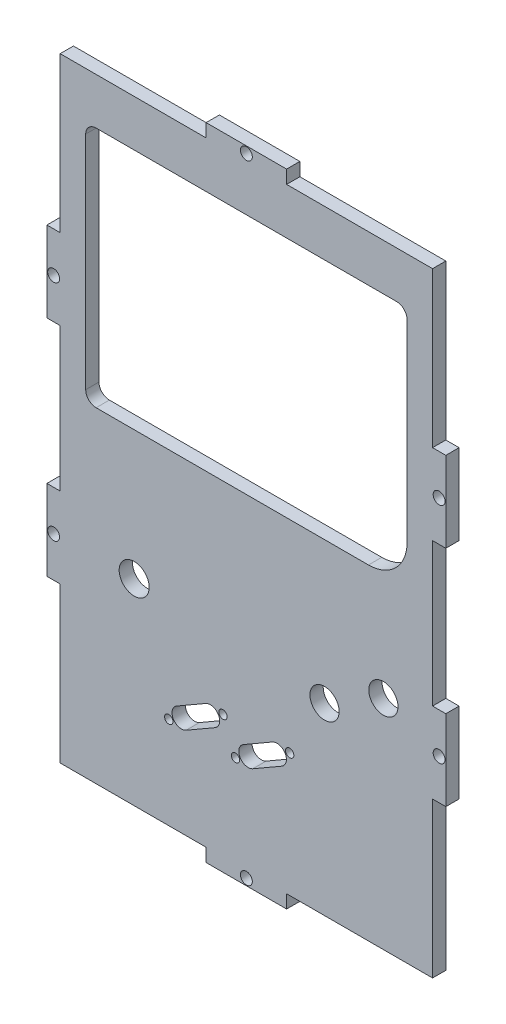
SolidWorks part; units mm, degrees
ref_plane "Front Plane" through (0, 0, 0) normal (0, 0, 1) x (1, 0, 0)
ref_plane "Top Plane" through (0, 0, 0) normal (0, 1, 0) x (1, 0, 0)
ref_plane "Right Plane" through (0, 0, 0) normal (1, 0, 0) x (0, 0, -1)
sketch "Sketch1" plane through (0, 0, 0) normal (0, 0, 1) x (1, 0, 0)
  line L0 (0, 73.6471) -> (0, 62.5071) construction
  line L1 (0, 62.5071) -> (0, 56.2171) construction
  line L2 (0, 56.2171) -> (0, 10.2844) construction
  line L3 (-12.1109, -47.7971) -> (3.8891, -47.7971) construction
  line L4 (-2.6061, -51.5471) -> (10.3843, -44.0471) construction
  line L5 (0.425, -49.7971) -> (7.3532, -45.7971) construction
  line L6 (0, 10.2844) -> (0, -73.6471) construction
  line L7 (-18.6061, -51.5471) -> (-5.6157, -44.0471) construction
  line L8 (-0.7, -47.8486) -> (6.2282, -43.8486)
  line L9 (1.55, -51.7457) -> (8.4782, -47.7457)
  line L15 (-16.3293, -29.1587) -> (-16.3293, -23.8757)
  line L16 (0, 0) -> (-44.645, 0) construction
  line L17 (0, 0) -> (44.645, 0) construction
  line L18 (-36.025, 60.0071) -> (-38.525, 60.0071) construction
  line L19 (29.275, 4.4344) -> (29.275, 13.6844) construction
  line L22 (-44.645, 73.6471) -> (44.645, 73.6471)
  line L23 (44.645, 73.6471) -> (44.645, -73.6471)
  line L24 (44.645, -73.6471) -> (-44.645, -73.6471)
  line L25 (-44.645, -73.6471) -> (-44.645, 73.6471)
  line L26 (-25.1657, 56.2171) -> (-25.1657, 10.2844)
  line L27 (-25.1657, 10.2844) -> (25.1657, 10.2844)
  line L28 (25.1657, 10.2844) -> (25.1657, 56.2171)
  line L29 (25.1657, 56.2171) -> (-25.1657, 56.2171)
  line L30 (29.275, 13.6844) -> (38.525, 13.6844) construction
  line L31 (-36.025, 62.5071) -> (-36.025, 60.0071) construction
  line L34 (36.025, 62.5071) -> (-36.025, 62.5071)
  line L35 (-38.525, 60.0071) -> (-38.525, 6.9344)
  line L36 (-36.025, 4.4344) -> (29.275, 4.4344)
  line L37 (38.525, 13.6844) -> (38.525, 60.0071)
  line L42 (-15.575, -49.7971) -> (-8.6468, -45.7971) construction
  line L43 (-16.7, -47.8486) -> (-9.7718, -43.8486)
  line L44 (-14.45, -51.7457) -> (-7.5218, -47.7457)
  line L45 (-16.7, -47.8486) -> (-14.45, -51.7457) construction
  line L46 (-9.7718, -43.8486) -> (-7.5218, -47.7457) construction
  line L150 (42.2525, -55.0539) -> (42.2511, -54.9499)
  circle A1 centre (-5.6157, -44.0471) radius 1
  circle A2 centre (-26.9008, -26.5172) radius 3.6
  circle A4 centre (-18.6061, -51.5471) radius 1
  arc A13 (-16.7, -47.8486) -> (-14.45, -51.7457) centre (-15.575, -49.7971) ccw
  arc A14 (-7.5218, -47.7457) -> (-9.7718, -43.8486) centre (-8.6468, -45.7971) ccw
  circle A15 centre (18.7439, -29.5449) radius 3.5
  circle A16 centre (32.8547, -21.4753) radius 3.5
  circle A18 centre (10.3843, -44.0471) radius 1
  circle A19 centre (-32.9517, 40.3431) radius 4.5
  circle A20 centre (-2.6061, -51.5471) radius 1
  arc A21 (-0.7, -47.8486) -> (1.55, -51.7457) centre (0.425, -49.7971) ccw
  arc A22 (8.4782, -47.7457) -> (6.2282, -43.8486) centre (7.3532, -45.7971) ccw
  arc A24 (38.525, 60.0071) -> (36.025, 62.5071) centre (36.025, 60.0071) ccw
  arc A25 (-36.025, 62.5071) -> (-38.525, 60.0071) centre (-36.025, 60.0071) ccw
  arc A26 (-38.525, 6.9344) -> (-36.025, 4.4344) centre (-36.025, 6.9344) ccw
  arc A27 (29.275, 4.4344) -> (38.525, 13.6844) centre (29.275, 13.6844) ccw
  point P31 (-12.1109, -47.7971)
  point P47 (3.8891, -47.7971)
  point P53 (3.8891, -47.7971)
  point P54 (-12.1109, -47.7971)
  dimension "D4" = 11.14
  dimension "D8" = 7
  dimension "D11" = 9
  dimension "D12" = 7.2
  dimension "D14" = 9.25
  dimension "D15" = 2.5
  dimension "D25" = 2
  dimension "D27" = 4.5
  dimension "D2" = 89.29
  dimension "D3" = 147.2943
  dimension "D5" = 25.9097
  dimension "D6" = 8.0696
  dimension "D7" = 14.1107
  dimension "D9" = 7.7861
  dimension "D10" = 22.1641
  dimension "D13" = 10.5715
  dimension "D16" = 6.29
  dimension "D17" = 6.12
  dimension "D18" = 5.85
  dimension "D19" = 32.5341
  dimension "D20" = 25.85
  dimension "D21" = 16
  dimension "D22" = 8
  dimension "D24" = 15
  dimension "D26" = 90
extrude "Body" add sketch "Sketch1<7>" along normal blind 3.18 contours L25 L24 L23 L22 A27 L36 A26 L35 A25 L34 A24 L37 A16 A15 A2 region at (0.0244, -16.6397, 0)
sketch "Sketch1<7>" plane through (0, 0, 0) normal (0, 0, 1) x (1, 0, 0) same geometry as "Sketch1"
extrude "Buttons" [suppressed] add sketch "Sketch1" along normal blind 3.18 contours A19 | A2 | A15 | A16
sketch "Sketch2" plane through (0, 73.6471, 0) normal (0, 1, 0) x (1, 0, 0)
  line L0 (-9.65, 0) -> (9.65, 0)
  line L1 (-44.645, 0) -> (44.645, 0) construction
  line L2 (9.65, 0) -> (9.65, -3.18)
  line L3 (-44.645, -3.18) -> (44.645, -3.18) construction
  line L4 (9.65, -3.18) -> (-9.65, -3.18)
  line L5 (-9.65, -3.18) -> (-9.65, 0)
  line L6 (0, 0) -> (0, -3.18) construction
  dimension "D1" = 19.3
extrude "Boss-Extrude1" add sketch "Sketch2" along normal blind 3.18
sketch "Sketch3" plane through (0, 0, 3.18) normal (0, 0, 1) x (1, 0, 0)
  line L0 (-9.65, 75.2371) -> (9.65, 75.2371) construction
  line L1 (-9.65, 76.8271) -> (-9.65, 73.6471) construction
  line L2 (9.65, 76.8271) -> (9.65, 73.6471) construction
  line L3 (0, 76.8271) -> (0, 73.4734) construction
  line L4 (-9.65, 76.8271) -> (9.65, 76.8271) construction
  circle A0 centre (0, 75.2371) radius 1.425
extrude "Cut-Extrude1" cut sketch "Sketch3" against normal through all
sketch "Sketch4" plane through (-44.645, 0, 0) normal (-1, 0, 0) x (0, 0, 1)
  line L0 (0, 17.1771) -> (0, 36.4771)
  line L1 (0, -73.6471) -> (0, 73.6471) construction
  line L2 (0, 36.4771) -> (3.18, 36.4771)
  line L3 (3.18, -73.6471) -> (3.18, 73.6471) construction
  line L4 (3.18, 36.4771) -> (3.18, 17.1771)
  line L5 (3.18, 17.1771) -> (0, 17.1771)
  line L6 (3.18, 26.8271) -> (0, 26.8271) construction
  line L7 (0, 73.6471) -> (3.18, 73.6471) construction
  dimension "D1" = 19.3
  dimension "D2" = 46.82
extrude "Boss-Extrude2" add sketch "Sketch4" along normal blind 3.18
sketch "Sketch5" plane through (0, 0, 3.18) normal (0, 0, 1) x (1, 0, 0)
  line L0 (-47.825, 26.8271) -> (-44.6033, 26.8271) construction
  line L1 (-47.825, 17.1771) -> (-47.825, 36.4771) construction
  line L2 (-46.235, 17.1771) -> (-46.235, 36.4771) construction
  line L3 (-47.825, 17.1771) -> (-44.645, 17.1771) construction
  line L4 (-47.825, 36.4771) -> (-44.645, 36.4771) construction
  circle A0 centre (-46.2141, 26.8271) radius 1.425
extrude "Cut-Extrude2" cut sketch "Sketch5" against normal through all
mirror "Mirror1" about plane through (0, 0, 0) normal (1, 0, 0) of "Cut-Extrude2", "Boss-Extrude2"
mirror "Mirror2" about plane through (0, 0, 0) normal (0, 1, 0) of "Cut-Extrude1", "Boss-Extrude1", "Mirror1"
